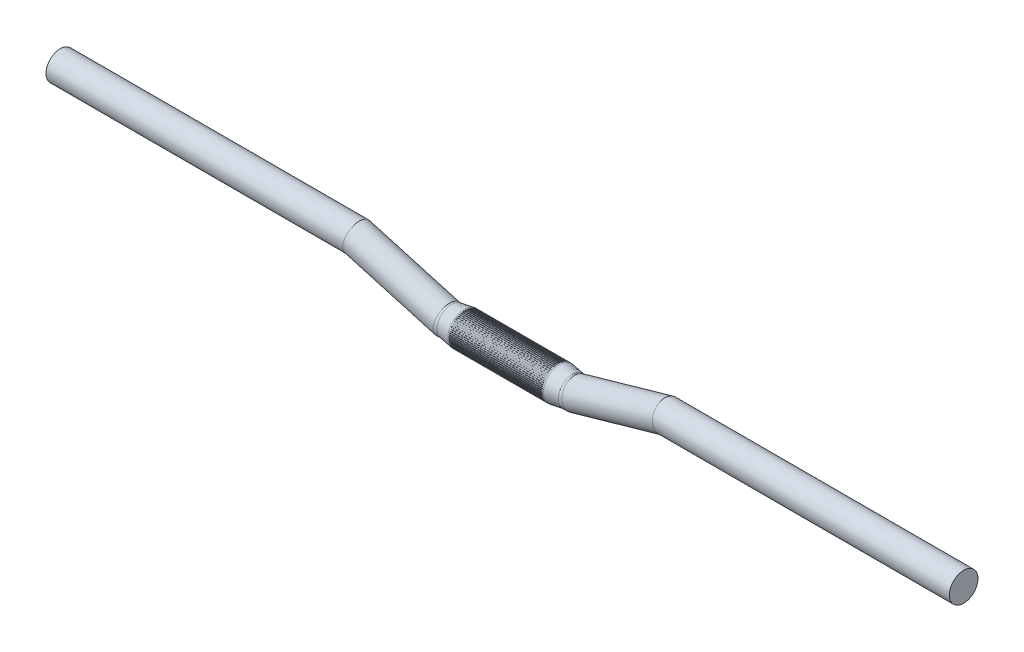
SolidWorks part; units mm, degrees
material "Alliage 2024"
ref_plane "Plan de face" through (0, 0, 0) normal (0, 0, 1) x (1, 0, 0)
ref_plane "Plan de dessus" through (0, 0, 0) normal (0, 1, 0) x (1, 0, 0)
ref_plane "Plan de droite" through (0, 0, 0) normal (1, 0, 0) x (0, 0, -1)
sketch "Esquisse1" plane through (0, 0, 0) normal (0, 0, 1) x (1, 0, 0)
  line L0 (-50, 0) -> (50, 0)
  line L1 (120, 20) -> (350, 20)
  line L2 (-120, 20) -> (-350, 20)
  spline S0 degree 1 poles (50, 0) (120, 20) knots 0 0 1 1
  spline S1 degree 1 poles (-50, 0) (-120, 20) knots 0 0 1 1
  dimension "D1" = 100
  dimension "D2" = 50
  dimension "D3" = 70
  dimension "D4" = 70
  dimension "D5" = 230
  dimension "D6" = 230
  dimension "D7" = 20
sketch "Esquisse2" plane through (0, 0, 0) normal (1, 0, 0) x (0, 0, -1)
  circle A0 centre (0, 0) radius 11.1
  dimension "D1" = 22.2
sweep "Balayage1" add profiles "Esquisse2" path "Esquisse1"
sketch "Esquisse4" plane through (0, 0, 0) normal (-1, 0, 0) x (0, 0, 1)
  circle A0 centre (0, 0) radius 12.7
  dimension "D1" = 25.4
extrude "Boss.-Extru.1" add sketch "Esquisse4" against normal blind 47
sketch "Esquisse5" plane through (0, 0, 0) normal (-1, 0, 0) x (0, 0, 1)
  line L1 (12.95, 0.25) -> (12.45, 0.25)
  line L2 (12.95, 0.25) -> (12.95, -0.25)
  line L3 (12.95, -0.25) -> (12.45, -0.25)
  line L4 (12.45, 0.25) -> (12.45, -0.25)
  line L5 (12.95, 0.25) -> (12.45, -0.25) construction
  line L6 (12.95, -0.25) -> (12.45, 0.25) construction
  circle A0 centre (0, 0) radius 12.7 construction
  point P0 (12.7, 0)
  dimension "D1" = 0.5
  dimension "D2" = 0.5
extrude "Enlèv. mat.-Extru.1" cut sketch "Esquisse5" against normal blind 36
pattern_circular "Répétition circulaire1" count 68 over 360 about axis through (0, 0, 0) along (-1, 0, 0) of "Enlèv. mat.-Extru.1"
mirror "Symétrie1" of "Répétition circulaire1", "Enlèv. mat.-Extru.1", "Boss.-Extru.1", "Balayage1"
chamfer "Chanfrein3" distance 10 angle 9 2 edges at (47, 0, 12.7) (-47, 0, 12.7) first distance on face at (47, 0, 11.1) first distance on face at (47, 0, 12.7)
ref_point "Point1"
ref_axis "Axe1" through (-363.2564, 20, 0) along (1, 0, 0)
